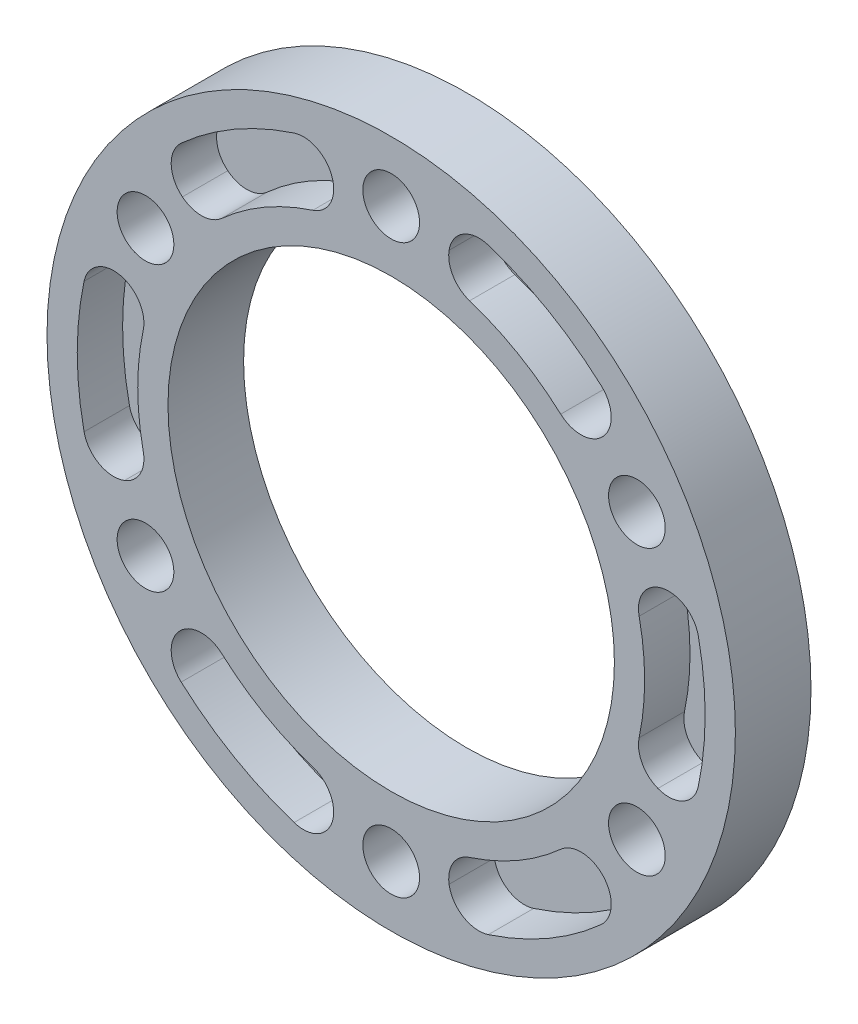
SolidWorks part; units mm, degrees
material "ABS"
ref_plane "Front Plane" through (0, 0, 0) normal (0, 0, 1) x (1, 0, 0)
ref_plane "Top Plane" through (0, 0, 0) normal (0, 1, 0) x (1, 0, 0)
ref_plane "Right Plane" through (0, 0, 0) normal (1, 0, 0) x (0, 0, -1)
sketch "Sketch1" plane through (0, 0, 0) normal (0, 0, 1) x (1, 0, 0)
  circle A0 centre (0, 0) radius 23.8252 construction
  circle A1 centre (0, 23.8252) radius 2.3813
  circle A2 centre (20.6332, 11.9126) radius 2.3813
  circle A3 centre (20.6332, -11.9126) radius 2.3813
  circle A4 centre (0, -23.8252) radius 2.3813
  circle A5 centre (-20.6332, -11.9126) radius 2.3813
  circle A6 centre (-20.6332, 11.9126) radius 2.3813
  circle A7 centre (0, 0) radius 18.7452
  circle A8 centre (0, 0) radius 28.9052
  point P17 (0, 0)
  dimension "D1" = 47.6504
  dimension "D2" = 4.7625
  dimension "D4" = 5.08
  dimension "D5" = 5.08
  dimension "D3" = 6
extrude "Boss-Extrude1" add sketch "Sketch1" along normal blind 6.35
shell "Shell1" thickness 2.54 removed face at (-18.252, -11.9126, 6.35)
fillet "Fillet1" radius 2.54 24 edges at (20.0939, -7.021, 4.445) (24.7192, -9.1697, 4.445) (24.7192, 9.1697, 4.445) (20.0939, 7.021, 4.445) (4.4184, -25.9923, 4.445) (3.9666, -20.9123, 4.445) (16.1273, -13.8913, 4.445) (20.3008, -16.8226, 4.445) (-4.4184, -25.9923, 4.445) (-3.9666, -20.9123, 4.445) (-20.3008, -16.8226, 4.445) (-16.1273, -13.8913, 4.445) (-24.7192, -9.1697, 4.445) (-20.0939, -7.021, 4.445) (-24.7192, 9.1697, 4.445) (-20.0939, 7.021, 4.445) (-20.3008, 16.8226, 4.445) (-16.1273, 13.8913, 4.445) (-3.9666, 20.9123, 4.445) (-4.4184, 25.9923, 4.445) (3.9666, 20.9123, 4.445) (4.4184, 25.9923, 4.445) (16.1273, 13.8913, 4.445) (20.3008, 16.8226, 4.445)
